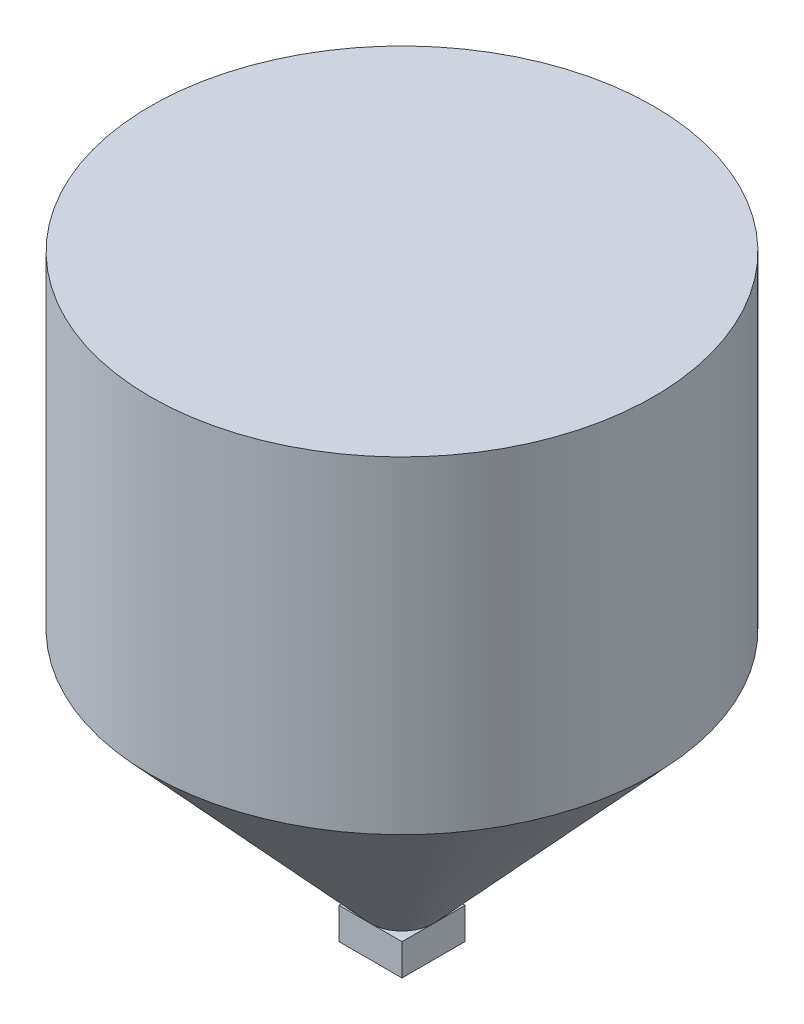
SolidWorks part; units mm, degrees
ref_plane "Alzado" through (0, 0, 0) normal (0, 0, 1) x (1, 0, 0)
ref_plane "Planta" through (0, 0, 0) normal (0, 1, 0) x (1, 0, 0)
ref_plane "Vista lateral" through (0, 0, 0) normal (1, 0, 0) x (0, 0, -1)
sketch "Croquis1" plane through (0, 0, 0) normal (0, 1, 0) x (1, 0, 0)
  circle A0 centre (0, 0) radius 400
  dimension "D1" = 800
ref_plane "Plano1" through (0, -900, 0) normal (0, 1, 0) x (1, 0, 0)
extrude "Saliente-Extruir1" add sketch "Croquis1" against normal blind 520 contours A0
sketch "Croquis2" plane through (0, -520, 0) normal (0, -1, 0) x (1, 0, 0)
  circle A0 centre (0, 0) radius 400
  dimension "D1" = 800
sketch "Croquis3" plane through (0, -900, 0) normal (0, 1, 0) x (1, 0, 0)
  circle A0 centre (0, 0) radius 50
  dimension "D1" = 100
loft "Recubrir1" add profiles "Croquis3", "Croquis2" connector at (-49.9253, -900, 2.7318) connector at (-399.2107, -520, 25.1162)
sketch "Croquis4" plane through (0, -900, 0) normal (0, -1, 0) x (1, 0, 0)
  line L1 (-50, -50) -> (50, -50)
  line L2 (-50, -50) -> (-50, 50)
  line L3 (-50, 50) -> (50, 50)
  line L4 (50, -50) -> (50, 50)
extrude "Saliente-Extruir2" add sketch "Croquis4" along normal blind 50
